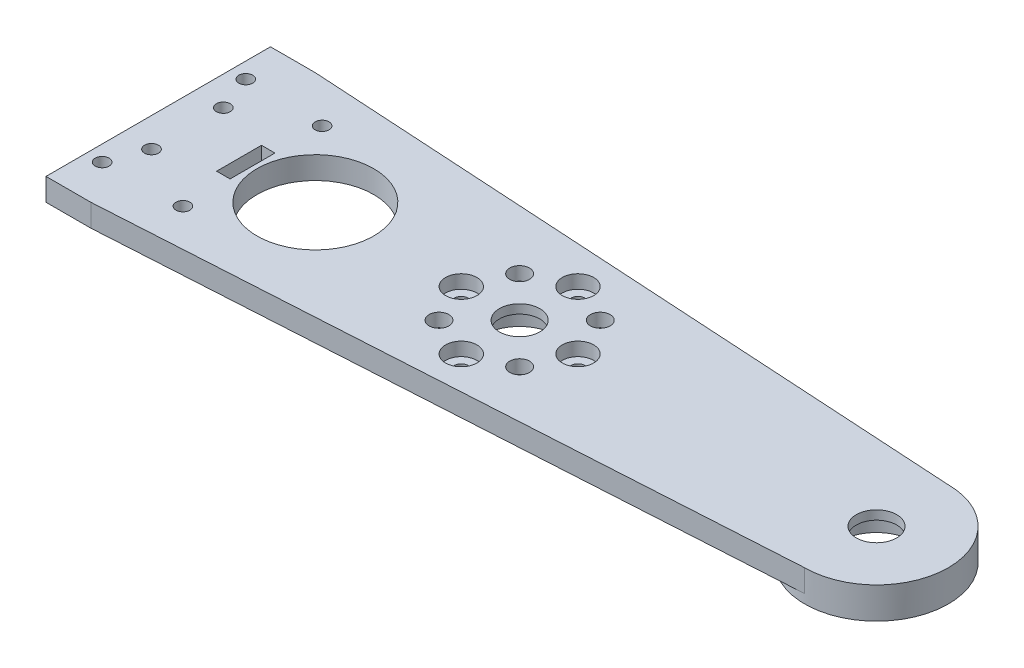
SolidWorks part; units mm, degrees
ref_plane "Front Plane" through (0, 0, 0) normal (0, 0, 1) x (1, 0, 0)
ref_plane "Top Plane" through (0, 0, 0) normal (0, 1, 0) x (1, 0, 0)
ref_plane "Right Plane" through (0, 0, 0) normal (1, 0, 0) x (0, 0, -1)
sketch "Sketch28" plane through (-32, 0, 0) normal (0, -1, 0) x (0, 0, 1)
  line L1 (0, -20) -> (0, -65.5) construction
  line L2 (-8, 8.5) -> (8, 8.5) construction
  line L3 (0, 15) -> (0, -3) construction
  line L8 (-25, 15) -> (25, 15)
  line L12 (25, 15) -> (25, 5)
  line L13 (-25, 15) -> (-25, 5)
  line L14 (-25, 5) -> (-16, -145)
  line L15 (16, -145) -> (25, 5)
  line L16 (-25, 5) -> (-25, 8.5) construction
  line L17 (-25, 8.5) -> (-8, 8.5) construction
  line L18 (-25, 15) -> (-25, 11.5) construction
  line L19 (-25, 11.5) -> (-16, 11.5) construction
  line L20 (-16, 11.5) -> (16, 11.5) construction
  line L21 (-5, -3) -> (5, -3)
  line L26 (5, -3) -> (5, -6)
  line L27 (5, -6) -> (-5, -6)
  line L28 (-5, -6) -> (-5, -3)
  line L29 (-5, -3) -> (-15.5, -3) construction
  line L30 (-15.5, -3) -> (-15.5, -6) construction
  line L31 (5, -3) -> (15.5, -3) construction
  line L32 (15.5, -3) -> (15.5, -6) construction
  line L33 (0, -20) -> (0, -6) construction
  line L34 (0, -65.5) -> (0, -145) construction
  circle A7 centre (8, 8.5) radius 1.55
  circle A8 centre (-8, 8.5) radius 1.55
  circle A9 centre (16, 11.5) radius 1.55
  circle A10 centre (-16, 11.5) radius 1.55
  circle A13 centre (-15.5, -6) radius 1.55
  circle A14 centre (15.5, -6) radius 1.55
  circle A15 centre (0, -20) radius 12.5 construction
  arc A17 (-16, -145) -> (16, -145) centre (0, -145) ccw
  circle A18 centre (0, -20) radius 13
  circle A19 centre (0, -145) radius 4.5
  circle A20 centre (0, -65.5) radius 4.5
  point P13 (0, 15)
  point P27 (0, -3)
extrude "Boss-Extrude10" add sketch "Sketch28" along normal blind 5
sketch "Sketch29" plane through (0, -5, 0) normal (0, -1, 0) x (1, 0, 0)
  circle A0 centre (113, 0) radius 16
  circle A2 centre (33.5, 0) radius 16
extrude "Boss-Extrude11" add sketch "Sketch29" along normal blind 2
sketch "Sketch30" plane through (0, -7, 0) normal (0, -1, 0) x (1, 0, 0)
  circle A0 centre (33.5, 0) radius 8.2
  circle A1 centre (113, 0) radius 8.2
extrude "Cut-Extrude1" cut sketch "Sketch30" against normal blind 5
sketch "Sketch31" plane through (0, -7, 0) normal (0, -1, 0) x (1, 0, 0)
  line L0 (33.5, 0) -> (42.4803, 8.9803) construction
  circle A0 centre (33.5, 0) radius 12.7 construction
  circle A1 centre (42.4803, 8.9803) radius 1.2
  circle A2 centre (42.4803, -8.9803) radius 1.2
  circle A3 centre (24.5197, -8.9803) radius 1.2
  circle A4 centre (24.5197, 8.9803) radius 1.2
  circle A5 centre (33.5, 0) radius 13 construction
  circle A6 centre (33.5, 13) radius 1.55
  circle A7 centre (46.5, 0) radius 1.55
  circle A8 centre (33.5, -13) radius 1.55
  circle A9 centre (20.5, 0) radius 1.55
  point P14 (33.5, 0)
  point P24 (33.5, 0)
  dimension "D1" = 4
  dimension "D2" = 4
extrude "Cut-Extrude2" cut sketch "Sketch31" against normal up to surface (7 mm away) up to face at (-43.5, 0, -17.55)
sketch "Sketch32" plane through (0, 0, 0) normal (0, 1, 0) x (1, 0, 0)
  circle A0 centre (33.5, 13) radius 3.5
  circle A1 centre (20.5, 0) radius 3.5
  circle A2 centre (33.5, -13) radius 3.5
  circle A3 centre (46.5, 0) radius 3.5
  circle A4 centre (24.5197, 8.9803) radius 2.2
  circle A5 centre (42.4803, 8.9803) radius 2.2
  circle A6 centre (42.4803, -8.9803) radius 2.2
  circle A7 centre (24.5197, -8.9803) radius 2.2
  point P12 (33.5, 0)
  point P22 (33.5, 0)
  dimension "D1" = 4
  dimension "D2" = 4
extrude "Cut-Extrude3" cut sketch "Sketch32" against normal blind 3
